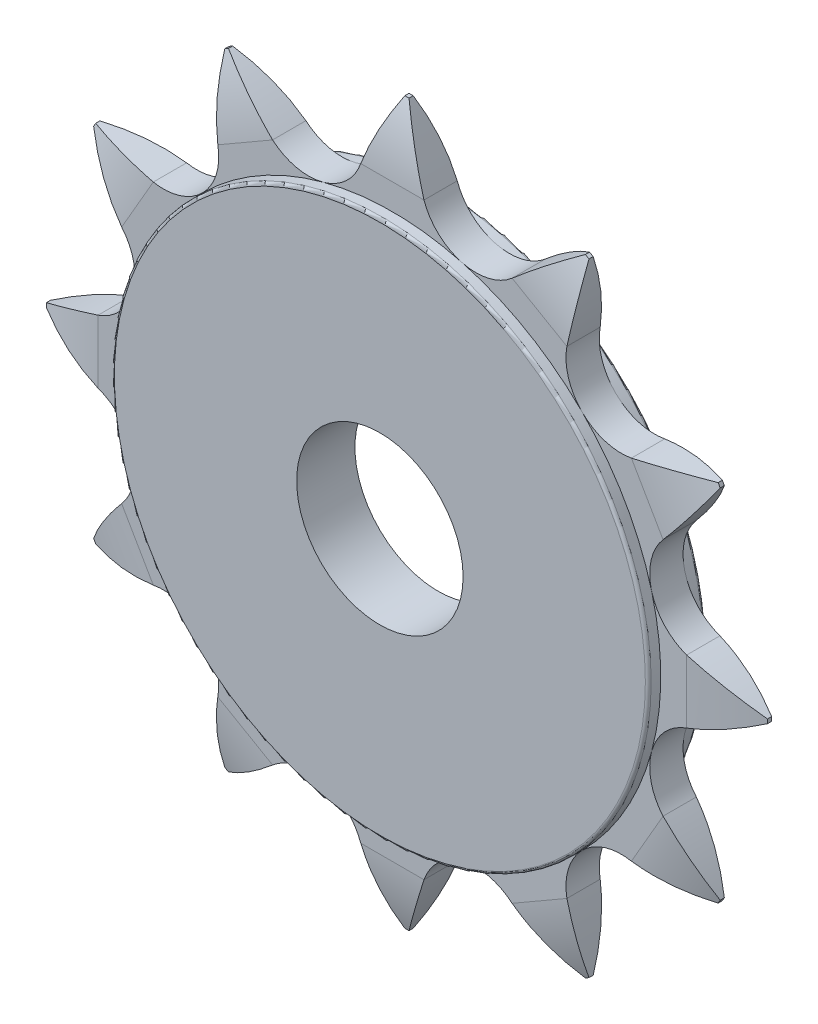
SolidWorks part; units mm, degrees
material "AISI 1020"
ref_plane "Спереди" through (0, 0, 0) normal (0, 0, 1) x (1, 0, 0)
ref_plane "Сверху" through (0, 0, 0) normal (0, 1, 0) x (1, 0, 0)
ref_plane "Справа" through (0, 0, 0) normal (1, 0, 0) x (0, 0, -1)
sketch "Эскиз1" plane through (0, 0, 0) normal (0, 0, 1) x (1, 0, 0)
  line L0 (0, 83.8109) -> (0, -76.1997) construction
  line L1 (-94.1655, 0) -> (96.1126, 0) construction
  line L3 (-10, 37.3205) -> (-27.3205, 27.3205)
  line L4 (-27.3205, 27.3205) -> (-37.3205, 10)
  line L5 (-37.3205, 10) -> (-37.3205, -10)
  line L6 (-37.3205, -10) -> (-27.3205, -27.3205)
  line L7 (-27.3205, -27.3205) -> (-10, -37.3205)
  line L8 (-10, -37.3205) -> (10, -37.3205)
  line L9 (10, -37.3205) -> (27.3205, -27.3205)
  line L10 (27.3205, -27.3205) -> (37.3205, -10)
  line L11 (37.3205, -10) -> (37.3205, 10)
  line L12 (37.3205, 10) -> (27.3205, 27.3205)
  line L13 (27.3205, 27.3205) -> (10, 37.3205)
  line L14 (10, 37.3205) -> (-10, 37.3205)
  circle A0 centre (0, 0) radius 37.3205 construction
  circle A1 centre (0, 0) radius 32.25 construction
  dimension "D2" = 64.5
  dimension "D1" = 20
sketch "Эскиз2" plane through (0, 0, 0) normal (0, 0, 1) x (1, 0, 0)
  line L0 (-10, 37.3205) -> (10, 37.3205) construction
  line L1 (0, 56.2252) -> (0, 15.3899) construction
  line L2 (0, 83.8109) -> (0, -76.1997) construction
  circle A0 centre (-10, 37.3205) radius 2.5 construction
  circle A1 centre (-10, 37.3205) radius 6 construction
  circle A2 centre (10, 37.3205) radius 2.5 construction
  circle A3 centre (10, 37.3205) radius 6 construction
  arc A4 (-7.5, 31.8662) -> (7.5, 31.8662) centre (0, 15.5031) cw construction
  arc A5 (-7.5, 42.7749) -> (7.5, 42.7749) centre (0, 59.1379) ccw construction
  dimension "D1" = 5
  dimension "D2" = 12
  dimension "D3" = 18
sketch "Эскиз3" plane through (0, 0, 0) normal (0, 0, 1) x (1, 0, 0)
  line L0 (0, 37.3205) -> (0, 43.3205) construction
  line L1 (10, 37.3205) -> (-10, 37.3205) construction
  line L2 (0, 83.8109) -> (0, -76.1997) construction
  line L3 (2, 43.3205) -> (-2, 43.3205) construction
  line L4 (-2, 43.3205) -> (-5, 31.86) construction
  line L5 (2, 43.3205) -> (5, 31.86) construction
  line L6 (-10, 37.3205) -> (0, 0) construction
  circle A0 centre (0, 0) radius 32.25 construction
  arc A1 (-0.25, 43.3205) -> (-3.8, 35.36) centre (47.2979, 17.3445) ccw
  arc A2 (-3.8, 35.36) -> (-8.3469, 31.1511) centre (-10.0667, 37.5695) cw
  dimension "D1" = 6
  dimension "D2" = 4
  dimension "D3" = 10
  dimension "D4" = 3.5
  dimension "D5" = 3.8
  dimension "D6" = 0.25
sketch "Эскиз4" plane through (0, 0, 0) normal (0, 0, 1) x (1, 0, 0)
  line L0 (0, 47.3475) -> (0, 29.3186) construction
  line L1 (0, 83.8109) -> (0, -76.1997) construction
  line L2 (-0.25, 43.3205) -> (0.25, 43.3205)
  arc A0 (-0.25, 43.3205) -> (-3.8, 35.36) centre (47.2979, 17.3445) ccw construction
  arc A1 (-8.3469, 31.1511) -> (-3.8, 35.36) centre (-10.0667, 37.5695) ccw construction
  arc A2 (-0.25, 43.3205) -> (-3.8, 35.36) centre (47.2979, 17.3445) ccw
  arc A3 (-8.3469, 31.1511) -> (-3.8, 35.36) centre (-10.0667, 37.5695) ccw
  arc A4 (8.3469, 31.1511) -> (3.8, 35.36) centre (10.0667, 37.5695) cw
  arc A5 (0.25, 43.3205) -> (3.8, 35.36) centre (-47.2979, 17.3445) cw
  arc A6 (8.3469, 31.1511) -> (-8.3469, 31.1511) centre (0, 0) ccw
extrude "Бобышка-Вытянуть1" add sketch "Эскиз4" along normal mid plane 4
sketch "Эскиз5" plane through (0, 0, 0) normal (1, 0, 0) x (0, 0, -1)
  line L0 (0, 69.1728) -> (0, -44.5412) construction
  line L1 (0, 83.8109) -> (0, -76.1997) construction
  line L2 (-2, 43.3205) -> (2, 43.3205) construction
  line L3 (-2, 35.36) -> (-3, 35.36)
  line L4 (-3, 35.36) -> (-3, 44.3205)
  line L5 (-3, 44.3205) -> (3, 44.3205)
  line L6 (-2, 43.3205) -> (-2, 35.36) construction
  line L7 (2, 35.36) -> (3, 35.36)
  line L8 (3, 35.36) -> (3, 44.3205)
  line L9 (-0.25, 43.3205) -> (0.25, 43.3205)
  arc A0 (-2, 35.36) -> (-0.25, 43.3205) centre (22.9654, 34.0443) cw
  arc A1 (2, 35.36) -> (0.25, 43.3205) centre (-22.9654, 34.0443) ccw
  point P20 (0, 44.3205)
  dimension "D2" = 25
  dimension "D1" = 0.25
  dimension "D3" = 1
  dimension "D4" = 1
extrude "Вырез-Вытянуть1" cut sketch "Эскиз5" against normal mid plane 12
ref_axis "Ось1" through (0, 0, 0) along (0, 0, 1)
pattern_circular "Круговой массив1" count 12 over 360 about axis through (0, 0, 0) along (0, 0, 1) of bodies 104
sketch "Эскиз6" plane through (0, 0, 0) normal (0, 0, 1) x (1, 0, 0)
  circle A0 centre (0, 0) radius 10
  circle A1 centre (0, 0) radius 32.25
  dimension "D1" = 20
  dimension "D2" = 64.5
extrude "Бобышка-Вытянуть2" add sketch "Эскиз6" along normal mid plane 7
fillet "Скругление1" radius 0.35 2 edges at (32.25, 0, -3.5) (32.25, 0, 3.5)
